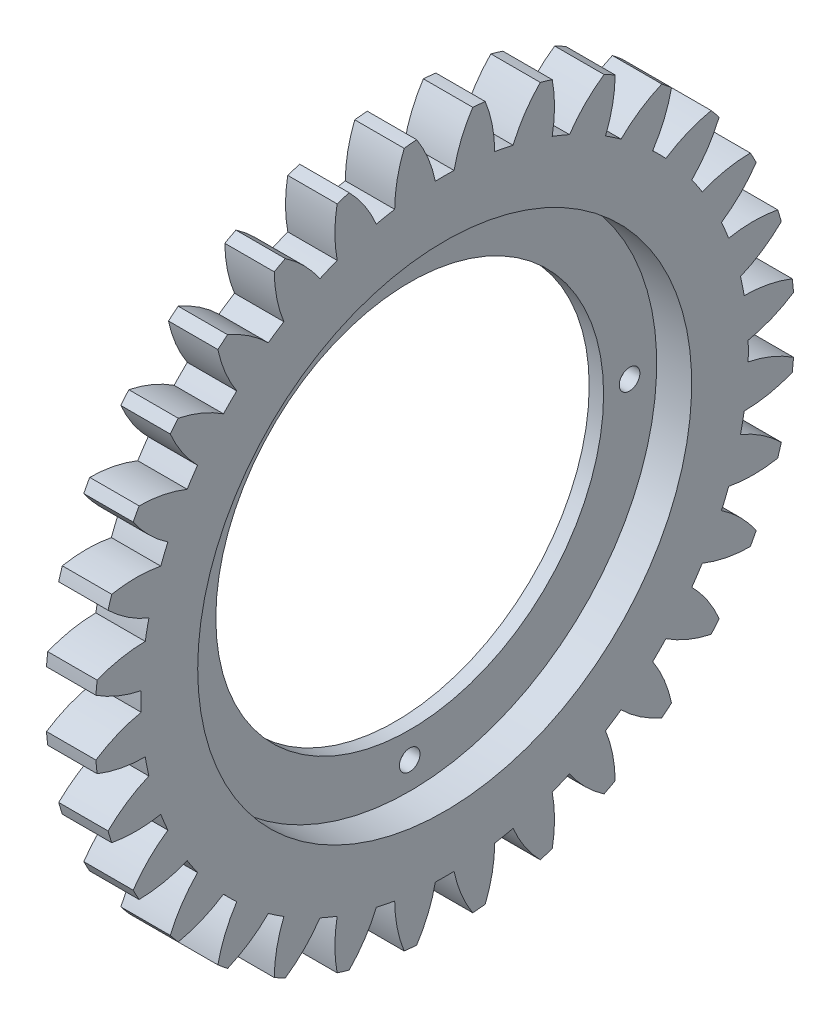
SolidWorks part; units mm, degrees
ref_plane "Plane1" through (0, 0, 0) normal (0, 0, 1) x (1, 0, 0)
ref_plane "Plane2" through (0, 0, 0) normal (0, 1, 0) x (1, 0, 0)
ref_plane "Plane3" through (0, 0, 0) normal (1, 0, 0) x (0, 0, -1)
sketch "HoldingSke" plane through (0, 0, 0) normal (0, 1, 0) x (1, 0, 0)
  line L0 (0, 0) -> (0.1696, -0.106)
  line L1 (-15, 0) -> (100, 0) construction
  line L2 (0, 0) -> (-2.1039, 2.3779)
  line L3 (0, 0) -> (-11.863, 4.5341)
  line L4 (0, 0) -> (7.3237, 4.5764)
  line L5 (0, 0) -> (-46.8476, -17.4728)
  line L6 (0, 0) -> (-9.9476, -6.7116)
  line L7 (-2.1039, 2.3779) -> (8.6586, 51.2059)
  line L8 (-76.2, 54.61) -> (-68.8, 54.61)
  line L9 (-71.009, 38.7566) -> (-53.1078, 45.2721)
  line L10 (-76.2, 71.12) -> (104.1128, 71.12)
  line L11 (0, 0) -> (-12, 0)
  line L12 (-76.2, 101.6) -> (-76.033, 101.6)
  line L13 (24.9733, 27.94) -> (52.9518, 28.4284)
  line L14 (24.9733, 27.94) -> (24.9743, 27.94)
  line L15 (24.9733, 27.94) -> (100.4006, 29.5858)
  line L16 (-63.627, -5) -> (-12.827, -5)
  circle A0 centre (0, 0) radius 60
  circle A1 centre (0, 0) radius 37.5
  circle A2 centre (0, 0) radius 37.5
  circle A3 centre (0, 0) radius 60
  dimension "Num_teeth" = 32
  dimension "Pitch_radius" = 180.3128
  dimension "Width" = 12
  dimension "Thickness" = 12
sketch "BasProSke" plane through (0, 0, 0) normal (0, 1, 0) x (1, 0, 0)
  line L0 (-10, 0) -> (3.5, 0) construction
  line L1 (0, 0) -> (0, 85)
  line L2 (0, 0) -> (3.5, 0)
  line L3 (12, 60) -> (12, 85)
  line L4 (12, 85) -> (0, 85)
  line L5 (3.5, 0) -> (3.5, 60)
  line L6 (3.5, 60) -> (12, 60)
  line L7 (12, 0) -> (60, 0) construction
  dimension "Thickness" = 12
  dimension "Diameter" = 170
  dimension "D1" = 8.5
  dimension "D2" = 60
  dimension "D4" = 12
revolve "Base-Revolve" add sketch "BasProSke" angle 360 about L0
sketch "TooCutSke" plane through (0, 0, 0) normal (1, 0, 0) x (0, 0, -1)
  line L1 (0, 0) -> (0, 107) construction
  line L2 (0, 0) -> (-4.2176, 79.8887) construction
  line L3 (0, 0) -> (-15.6666, 159.0653) construction
  line L4 (-4.2176, 79.8887) -> (-7.8333, 79.5326) construction
  arc A0 (2.2739, 73.7139) -> (-2.2739, 73.7139) centre (0, 0) ccw
  arc A1 (6.8274, 84.7508) -> (-6.8274, 84.7508) centre (0, 0) ccw
  circle A2 centre (0, 0) radius 80 construction
  circle A3 centre (0, 0) radius 75.1754 construction
  arc A4 (-2.2739, 73.7139) -> (-6.8274, 84.7508) centre (-33.6127, 67.2423) ccw
  arc A5 (6.8274, 84.7508) -> (2.2739, 73.7139) centre (33.6127, 67.2423) ccw
extrude "ToothCut" cut sketch "TooCutSke" along normal through all
fillet "Breaks" [suppressed] radius 0.1 tangent propagation no
fillet "RootFillets" [suppressed] radius 1.251
pattern_circular "TeethCuts" count 32 every 11.25 about axis through (-10, 0, 0) along (1, 0, 0) of "ToothCut", "RootFillets", "Breaks"
sketch "HubNeaOneSke" plane through (0, 0, 0) normal (-1, 0, 0) x (0, 0, 1)
  circle A0 centre (0, 0) radius 37.5
  dimension "Diameter" = 75
extrude "HubNearOne" [suppressed] add sketch "HubNeaOneSke" along normal blind 38.0001
sketch "HubNeaBotSke" plane through (0, 0, 0) normal (-1, 0, 0) x (0, 0, 1)
  circle A0 centre (0, 0) radius 37.5
  dimension "Diameter" = 75
extrude "HubNearBoth" [suppressed] add sketch "HubNeaBotSke" along normal blind 19
ref_plane "FarPln" through (12, 0, 0) normal (1, 0, 0) x (0, 0, -1)
sketch "HubFarSke" plane through (12, 0, 0) normal (1, 0, 0) x (0, 0, -1)
  circle A0 centre (0, 0) radius 37.5
  dimension "Diameter" = 75
extrude "HubFar" [suppressed] add sketch "HubFarSke" along normal blind 19
sketch "BorSke" plane through (0, 0, 0) normal (1, 0, 0) x (0, 0, -1)
  circle A0 centre (0, 0) radius 47.1
  dimension "Diameter" = 94.2
extrude "Bore" cut sketch "BorSke" along normal mid plane 100.0001
sketch "KeySke" plane through (0, 0, 0) normal (1, 0, 0) x (0, 0, -1)
  line L0 (-16, 0) -> (-16, 67.4)
  line L1 (-16, 67.4) -> (16, 67.4)
  line L2 (16, 67.4) -> (16, 0)
  line L3 (0, 0) -> (0, 34) construction
  line L4 (-16, 0) -> (16, 0)
  dimension "Width" = 32
extrude "Keyway" [suppressed] cut sketch "KeySke" along normal mid plane 100.0001
pattern_circular "Keyway2" [suppressed] count 2 every 90 about axis through (-10, 0, 0) along (1, 0, 0) reverse direction yes
sketch "Sketch1" plane through (12, 0, 0) normal (1, 0, 0) x (0, 0, -1)
  circle A0 centre (0, 53.4) radius 2.5
  circle A1 centre (53.4, 0) radius 2.5
  circle A2 centre (0, -53.4) radius 2.5
  circle A3 centre (-53.4, 0) radius 2.5
  point P11 (0, 0)
  dimension "D1" = 5
  dimension "D3" = 53.4
  dimension "D4" = 73.7139
  dimension "D5" = 11.0127
  dimension "D6" = 6.8115
  dimension "D7" = 9.0854
  dimension "D2" = 4
extrude "Cut-Extrude1" cut sketch "Sketch1" against normal up to next
equation "' \"Module@HoldingSke\" = 6.35"
equation "' \"Num_teeth@HoldingSke\" = 12"
equation "' \"Ap@HoldingSke\" =  20"
equation "' \"Ap@HoldingSke\" = 20"
equation "' \"Width@HoldingSke\" = 0.5 * 25.4"
equation "' \"Hub_dia@HoldingSke\"= 1 * 25.4"
equation "' \"Hub_dia@HoldingSke\" = 1 * 25.4"
equation "' \"Overall_len@HoldingSke\" = 1.0 * 25.4"
equation "' \"Bore@HoldingSke\" = 0.75 * 25.4"
equation "' \"T_dim@HoldingSke\" = 0.1 * 25.4"
equation "' \"Width@KeySke\" = 0.25 * 25.4"
equation "' \"Show_teeth@HoldingSke\" = 13"
equation "' \"Backlash@HoldingSke\" = 0.009 * 25.4"
equation "' \"Addendum_fac@HoldingSke\" = 1.0"
equation "' \"Dedendum_fac@HoldingSke\" = 1.25"
equation "' \"Dedendum_add@HoldingSke\" = 0.00005 * 25.4"
equation "' \"Clearance_fac@HoldingSke\" = 0.25"
equation "\"Pitch@HoldingSke\" = 1 / \"Module@HoldingSke\""
equation "\"Overcut_dia@TooCutSke\" = (\"Num_teeth@HoldingSke\" + 2 * \"Addendum_fac@HoldingSke\") / \"Pitch@HoldingSke\" + 0.002 * 25.4"
equation "\"Pitch_dia@TooCutSke\" = \"Num_teeth@HoldingSke\" / \"Pitch@HoldingSke\""
equation "\"Base_dia@TooCutSke\" = \"Num_teeth@HoldingSke\" / \"Pitch@HoldingSke\" * cos((\"Ap@HoldingSke\"  * 3.14159265 / 180))"
equation "\"Root_dia@TooCutSke\" = (\"Num_teeth@HoldingSke\" + 2) / \"Pitch@HoldingSke\" - 2 * (\"Addendum_fac@HoldingSke\" + \"Dedendum_fac@HoldingSke\") / \"Pitch@HoldingSke\" - \"Dedendum_add@HoldingSke\" * 2"
equation "\"Half_ang@TooCutSke\" = 180 / \"Num_teeth@HoldingSke\""
equation "\"Half_CT@TooCutSke\" = \"Num_teeth@HoldingSke\" / \"Pitch@HoldingSke\" * sin((3.14159265 / 2 / \"Num_teeth@HoldingSke\")) / 2 - 7 * \"Backlash@HoldingSke\" / 4"
equation "\"Flank_rad@TooCutSke\" = \"Num_teeth@HoldingSke\" / \"Pitch@HoldingSke\" / 5"
equation "\"Radius@RootFillets\" = \"Clearance_fac@HoldingSke\" / \"Pitch@HoldingSke\" + \"Dedendum_add@HoldingSke\""
equation "\"Break_rad@Breaks\" = 0.02 / \"Pitch@HoldingSke\""
equation "\"Thickness@HoldingSke\" = \"Width@HoldingSke\""
equation "\"OAL@HoldingSke\" = \"Thickness@HoldingSke\""
equation "\"MHD@HoldingSke\" = (\"Num_teeth@HoldingSke\" + 2) / \"Pitch@HoldingSke\" - 2 * (\"Addendum_fac@HoldingSke\" + \"Dedendum_fac@HoldingSke\")  / \"Pitch@HoldingSke\" - \"Dedendum_add@HoldingSke\" * 2"
equation "\"MBD@HoldingSke\" = (\"Num_teeth@HoldingSke\" + 2) / \"Pitch@HoldingSke\" - 2 * (\"Addendum_fac@HoldingSke\" + \"Dedendum_fac@HoldingSke\")  / \"Pitch@HoldingSke\" - \"Dedendum_add@HoldingSke\" * 2 - 0.002 * 25.4"
equation "\"MHD@HoldingSke\" = ((sgn( \"MHD@HoldingSke\" - \"Hub_dia@HoldingSke\" )-1)*( \"MHD@HoldingSke\" - \"Hub_dia@HoldingSke\" ))/-2+ \"Hub_dia@HoldingSke\""
equation "\"MBD@HoldingSke\" = ((sgn( \"MBD@HoldingSke\" - \"Bore@HoldingSke\" )-1)*( \"MBD@HoldingSke\" - \"Bore@HoldingSke\" ))/-2+ \"Bore@HoldingSke\""
equation "\"OAL@HoldingSke\" = ((sgn( \"OAL@HoldingSke\" - \"Overall_len@HoldingSke\" )+1)*( \"OAL@HoldingSke\" - \"Overall_len@HoldingSke\" ))/2 + \"Overall_len@HoldingSke\" + 0.000002 * 25.4"
equation "\"Num_teeth@TeethCuts\" = int( \"Show_teeth@HoldingSke\" ) + 1"
equation "\"Num_teeth@TeethCuts\" = ((sgn( \"Num_teeth@TeethCuts\" - \"Num_teeth@HoldingSke\" )-1)*( \"Num_teeth@TeethCuts\" - \"Num_teeth@HoldingSke\" ))/-2+ \"Num_teeth@HoldingSke\""
equation "\"Num_teeth@TeethCuts\" = ((sgn( \"Num_teeth@TeethCuts\" - 2.0)+1)*( \"Num_teeth@TeethCuts\" - 2.0))/2 +2.0"
equation "\"Angle@TeethCuts\" = 360.0 / \"Num_teeth@HoldingSke\""
equation "\"Diameter@BasProSke\" = (\"Num_teeth@HoldingSke\" + 2 * \"Addendum_fac@HoldingSke\") / \"Pitch@HoldingSke\""
equation "\"Thickness@BasProSke\"  = \"Thickness@HoldingSke\""
equation "' \"Fillet_rad@BasProSke\" =  \"Thickness@HoldingSke\" * 0.05"
equation "' \"Fillet_rad@BasProSke\" = \"Thickness@HoldingSke\" * 0.05"
equation "\"MHD@HoldingSke\" = ((sgn( \"MHD@HoldingSke\" - \"Root_dia@TooCutSke\" )-1)*( \"MHD@HoldingSke\" - \"Root_dia@TooCutSke\" ))/-2+ \"Root_dia@TooCutSke\""
equation "\"Diameter@HubNeaOneSke\" = \"MHD@HoldingSke\""
equation "\"Length@HubNearOne\" = \"OAL@HoldingSke\" - \"Thickness@BasProSke\""
equation "\"Diameter@HubNeaBotSke\" = \"MHD@HoldingSke\""
equation "\"Length@HubNearBoth\" = ( \"OAL@HoldingSke\" - \"Thickness@BasProSke\" ) / 2.0"
equation "\"Thickness@FarPln\" = \"Thickness@BasProSke\""
equation "\"Diameter@HubFarSke\" = \"MHD@HoldingSke\""
equation "\"Length@HubFar\" = ( \"OAL@HoldingSke\" - \"Thickness@BasProSke\" ) / 2.0"
equation "\"Diameter@BorSke\"=94.2"
equation "\"D1@Bore\" = \"OAL@HoldingSke\" * 2.0"
equation "\"D1@Keyway\" = \"OAL@HoldingSke\" * 2.0"
equation "\"Offset@KeySke\" = \"T_dim@HoldingSke\" + \"MBD@HoldingSke\" / 2.0"
